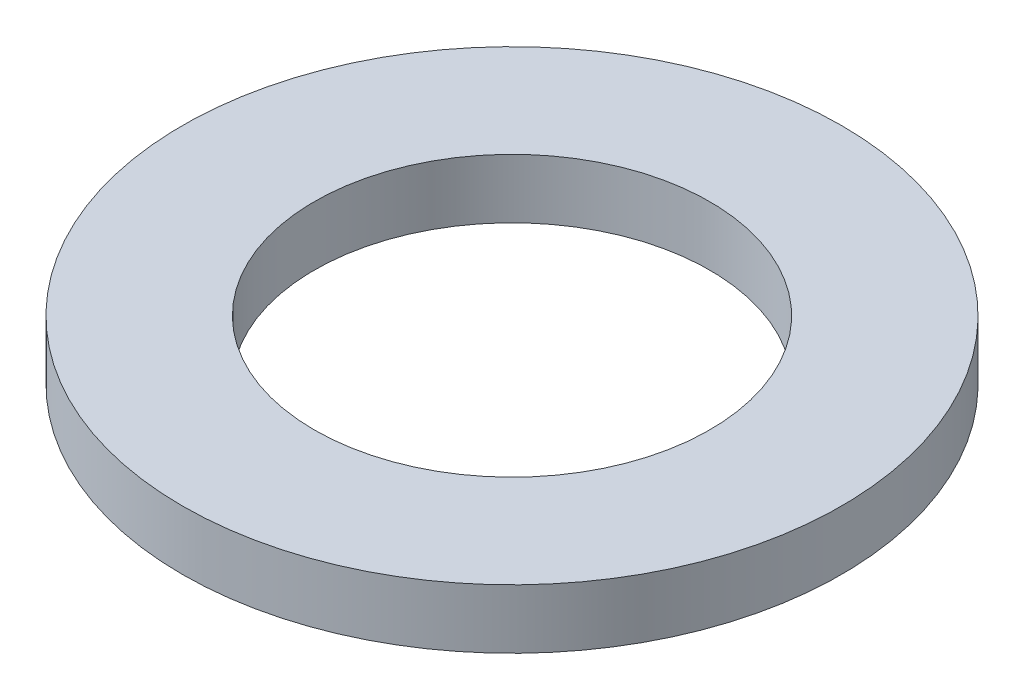
SolidWorks part; units mm, degrees
ref_plane "Front Plane" through (0, 0, 0) normal (0, 0, 1) x (1, 0, 0)
ref_plane "Top Plane" through (0, 0, 0) normal (0, 1, 0) x (1, 0, 0)
ref_plane "Right Plane" through (0, 0, 0) normal (1, 0, 0) x (0, 0, -1)
sketch "Sketch1" plane through (0, 0, 0) normal (0, 1, 0) x (1, 0, 0)
  circle A0 centre (0, 0) radius 50
  dimension "FLANGE_OD" = 100
extrude "Boss-Extrude1" add sketch "Sketch1" along normal blind 9
sketch "Sketch2" plane through (0, 0, 0) normal (0, 1, 0) x (1, 0, 0)
  circle A0 centre (0, 0) radius 30
  dimension "BORE_D" = 60
extrude "Cut-Extrude1" cut sketch "Sketch2" along normal through all
sketch "Sketch3" plane through (0, 9, 0) normal (0, 1, 0) x (1, 0, 0)
  circle A0 centre (0, 0) radius 20.4193 construction
  circle A1 centre (-20.4193, 0) radius 3.4252
  dimension "BOLT_D" = 6.8505
  dimension "BOLT_PCD" = 40.8387
extrude "Cut-Extrude2" cut sketch "Sketch3" against normal blind 8.6112 rebuild error yes
pattern_circular "CirPattern1" count 8 over 360 rebuild error yes
